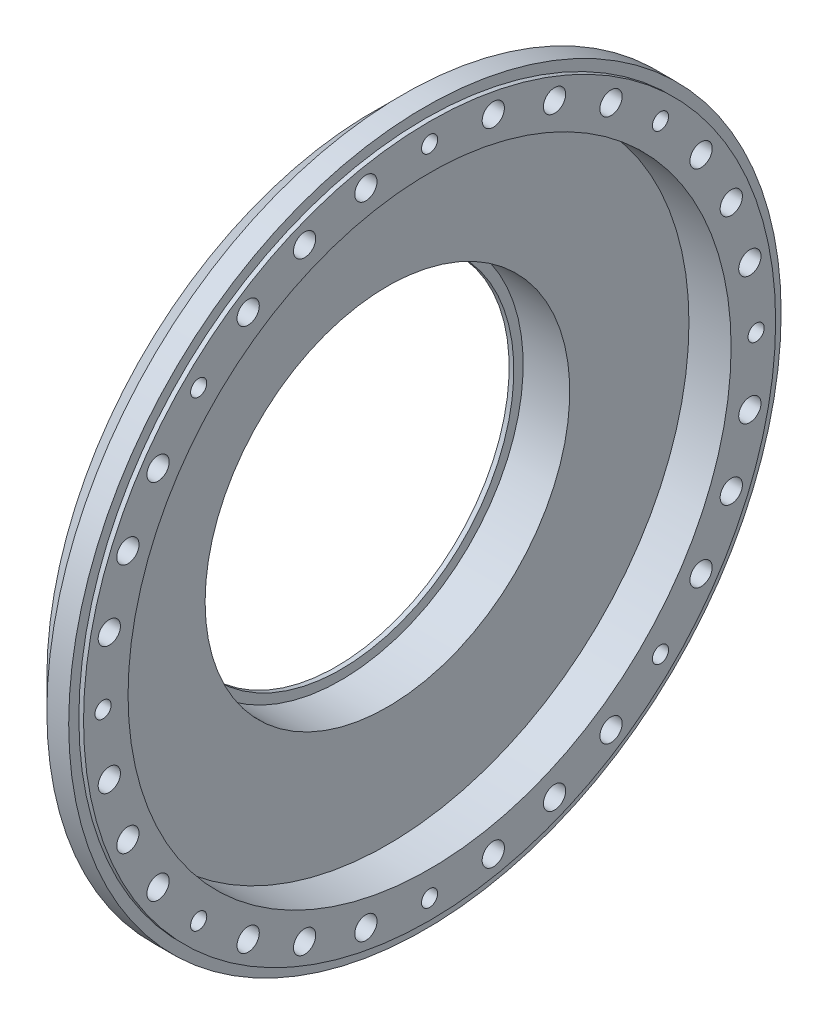
SolidWorks part; units mm, degrees
ref_plane "Front Plane" through (0, 0, 0) normal (0, 0, 1) x (1, 0, 0)
ref_plane "Top Plane" through (0, 0, 0) normal (0, 1, 0) x (1, 0, 0)
ref_plane "Right Plane" through (0, 0, 0) normal (1, 0, 0) x (0, 0, -1)
sketch "Sketch2" plane through (0, 0, 0) normal (0, 0, 1) x (1, 0, 0)
  line L0 (0, 0) -> (58.591, 0) construction
  line L2 (0, 0) -> (18.4, 0)
  line L3 (0, 0) -> (0, 2.5)
  line L4 (0, 2.5) -> (18.4, 2.5)
  line L5 (18.4, 0) -> (18.4, 2.5)
  line L6 (6.0094, 2.5) -> (6.0094, 6)
  line L11 (6.0094, 6) -> (9.9794, 6)
  line L16 (12.9794, 6) -> (12.9794, 3)
  line L17 (12.9794, 3) -> (13.6398, 3)
  line L18 (13.6398, 3) -> (13.6398, 2.5)
  line L19 (13.6398, 2.5) -> (6.0094, 2.5)
  line L22 (13.6398, 2.5) -> (16.1198, 2.5)
  line L23 (13.6398, 2.5) -> (13.6398, 4)
  line L24 (13.6398, 4) -> (16.1198, 4)
  line L25 (16.1198, 2.5) -> (16.1198, 4)
  line L27 (6.0094, 6) -> (9.9794, 6)
  line L28 (6.0094, 6) -> (6.0094, 9)
  line L29 (6.0094, 9) -> (9.9794, 9)
  line L30 (9.9794, 6) -> (9.9794, 9)
  line L31 (6.0094, 9) -> (6.0094, 8.25)
  line L32 (6.0094, 8.25) -> (5.0094, 8.25)
  line L33 (8.6609, 22.001) -> (8.6609, 12.476) construction
  line L34 (5.0094, 12.476) -> (12.3124, 12.476)
  line L35 (9.9794, 9) -> (12.3124, 9)
  line L36 (5.0094, 7.9375) -> (1.8344, 7.9375)
  line L37 (5.0094, 8.25) -> (5.0094, 12.476)
  line L38 (5.0094, 7.9375) -> (5.0094, 13.9365)
  line L39 (5.0094, 13.9365) -> (1.8344, 13.9365)
  line L40 (1.8344, 7.9375) -> (1.8344, 13.9365)
  line L41 (5.0094, 22.001) -> (12.3124, 22.001)
  line L42 (5.0094, 22.001) -> (5.0094, 30.1625)
  line L43 (5.0094, 30.1625) -> (12.3124, 30.1625)
  line L44 (12.3124, 22.001) -> (12.3124, 30.1625)
  line L49 (16.6398, 22.001) -> (16.6398, 7.5)
  line L51 (23.0198, 7.5) -> (23.0198, 6.5)
  line L54 (16.1198, 4) -> (13.6398, 4)
  line L56 (18.0398, 7.5) -> (23.0198, 7.5)
  line L57 (13.3124, 22.001) -> (16.6398, 22.001)
  line L58 (16.1198, 3.5) -> (20.0198, 3.5)
  line L59 (29.9098, 14) -> (26.9098, 11)
  line L60 (4.0094, 31.75) -> (18.0398, 31.75)
  line L61 (18.0398, 7.5) -> (23.0198, 7.5)
  line L62 (18.0398, 7.5) -> (18.0398, 12)
  line L63 (18.0398, 12) -> (23.0198, 12)
  line L64 (23.0198, 7.5) -> (23.0198, 12)
  line L65 (18.0398, 31.75) -> (18.0398, 12)
  line L66 (23.0198, 11) -> (26.9098, 11)
  line L67 (34.8098, 23) -> (31.3098, 19.5)
  line L68 (35.8098, 31) -> (38.7998, 33.99)
  line L69 (29.9098, 14) -> (29.9098, 15)
  line L70 (29.9098, 15) -> (22.9398, 15)
  line L71 (22.9398, 15) -> (21.0398, 15)
  line L72 (18.0398, 7.5) -> (16.6398, 7.5)
  line L73 (21.0398, 15) -> (21.0398, 43)
  line L74 (19.5798, 40) -> (9.6198, 40)
  line L75 (9.6198, 40) -> (4.0094, 40)
  line L76 (21.0398, 43) -> (19.5798, 43)
  line L77 (22.9398, 15) -> (29.9098, 15)
  line L78 (22.9398, 15) -> (22.9398, 21)
  line L79 (22.9398, 21) -> (29.9098, 21)
  line L80 (29.9098, 15) -> (29.9098, 21)
  line L81 (9.6198, 40) -> (19.5798, 40)
  line L82 (9.6198, 40) -> (9.6198, 50)
  line L83 (9.6198, 50) -> (19.5798, 50)
  line L84 (19.5798, 40) -> (19.5798, 50)
  line L85 (4.0094, 40) -> (4.0094, 31.75)
  line L86 (12.9794, 3) -> (12.9794, 2.5)
  line L87 (31.3098, 19.5) -> (29.9098, 19.5)
  line L88 (21.4694, 63.5) -> (21.4694, 51.308)
  line L89 (21.4694, 63.5) -> (25.9398, 63.5)
  line L90 (25.9398, 63.5) -> (25.9398, 25)
  line L91 (27.8398, 25) -> (25.9398, 25)
  line L92 (9.6198, 48) -> (8.1598, 48)
  line L93 (8.1598, 48) -> (8.1598, 53.476)
  line L94 (8.1598, 53.476) -> (19.5798, 53.476)
  line L95 (19.5798, 53.476) -> (19.5798, 50)
  line L96 (13.8698, 63.001) -> (13.8698, 53.476) construction
  line L97 (8.1598, 63.001) -> (19.5798, 63.001)
  line L98 (8.1598, 63.001) -> (8.1598, 68.2625)
  line L99 (8.1598, 68.2625) -> (19.5798, 68.2625)
  line L100 (19.5798, 63.001) -> (19.5798, 68.2625)
  line L101 (12.9794, 6) -> (11.9794, 6)
  line L102 (8.1598, 44.825) -> (4.9848, 44.825)
  line L103 (8.1598, 44.825) -> (8.1598, 54.9365)
  line L104 (8.1598, 54.9365) -> (4.9848, 54.9365)
  line L106 (9.9794, 6) -> (10.8794, 6)
  line L107 (27.8398, 25) -> (34.8098, 25)
  line L108 (34.8098, 25) -> (34.8098, 23)
  line L109 (0, 0) -> (-2, 0)
  line L110 (0, 0) -> (0, 11)
  line L111 (27.8398, 25) -> (34.8098, 25)
  line L112 (27.8398, 25) -> (27.8398, 32.5)
  line L113 (27.8398, 32.5) -> (34.8098, 32.5)
  line L114 (34.8098, 25) -> (34.8098, 32.5)
  line L115 (35.8098, 31) -> (34.8098, 31)
  line L116 (27.8398, 32.5) -> (27.8398, 64.5)
  line L117 (20.5373, 74.025) -> (6.2023, 74.025)
  line L118 (6.2023, 74.025) -> (6.2023, 76.2)
  line L119 (38.7998, 47.29) -> (30.8398, 55.25)
  line L120 (0, 11) -> (-2, 11)
  line L121 (38.7998, 43.815) -> (30.8623, 43.815)
  line L123 (-4.8152, 69.85) -> (1.5348, 76.2)
  line L124 (38.7998, 47.29) -> (38.7998, 33.99)
  line L125 (-2, 0) -> (-2, 11)
  line L126 (38.7998, 37.465) -> (30.8623, 37.465)
  line L127 (30.8623, 43.815) -> (30.8623, 37.465)
  line L128 (6.0094, 2.5) -> (6.0094, 0)
  line L129 (-0.0152, 63.5) -> (-0.0152, 30)
  line L132 (4.9848, 63.5) -> (-0.0152, 63.5)
  line L136 (-1.8152, 30) -> (-11.7752, 30)
  line L138 (-13.7752, 25.4) -> (-2, 25.4)
  line L139 (-2, 25.4) -> (-2, 11.5)
  line L140 (27.8398, 64.5) -> (20.5373, 64.5)
  line L141 (-1.8152, 30) -> (-11.7752, 30)
  line L142 (-1.8152, 30) -> (-1.8152, 39)
  line L143 (-1.8152, 39) -> (-11.7752, 39)
  line L144 (-11.7752, 30) -> (-11.7752, 39)
  line L145 (20.5373, 64.5) -> (20.5373, 74.025)
  line L146 (-12.7752, 37) -> (-12.7752, 47.29)
  line L147 (-12.7752, 37) -> (-11.7752, 37)
  line L148 (30.8398, 55.25) -> (30.8398, 76.2)
  line L149 (11.9794, 6) -> (11.9794, 5.45)
  line L154 (-2, 11.5) -> (0.5, 11.5)
  line L155 (4.9848, 60.6197) -> (24.0348, 60.6197)
  line L160 (4.9848, 60.6197) -> (4.9848, 55.8572)
  line L161 (4.9848, 55.8572) -> (24.0348, 55.8572)
  line L166 (24.0348, 60.6197) -> (24.0348, 55.8572)
  line L167 (4.9848, 60.6197) -> (24.0348, 55.8572) construction
  line L172 (4.9848, 55.8572) -> (24.0348, 60.6197) construction
  line L173 (24.0348, 62.2072) -> (25.9398, 62.2072)
  line L174 (11.9794, 5.45) -> (10.8794, 5.45)
  line L175 (10.8794, 6) -> (10.8794, 5.45)
  line L176 (24.0348, 62.2072) -> (24.0348, 54.2697)
  line L177 (24.0348, 54.2697) -> (25.9398, 54.2697)
  line L178 (25.9398, 62.2072) -> (25.9398, 54.2697)
  line L179 (24.0348, 62.2072) -> (25.9398, 54.2697) construction
  line L180 (24.0348, 54.2697) -> (25.9398, 62.2072) construction
  line L181 (3, 19.6197) -> (15.7, 19.6197)
  line L182 (3, 19.6197) -> (3, 14.8572)
  line L183 (3, 14.8572) -> (15.7, 14.8572)
  line L184 (15.7, 19.6197) -> (15.7, 14.8572)
  line L185 (3, 19.6197) -> (15.7, 14.8572) construction
  line L186 (3, 14.8572) -> (15.7, 19.6197) construction
  line L187 (15.7, 21.2072) -> (16.6398, 21.2072)
  line L188 (15.7, 21.2072) -> (15.7, 13.2697)
  line L189 (15.7, 13.2697) -> (16.6398, 13.2697)
  line L190 (16.6398, 21.2072) -> (16.6398, 13.2697)
  line L191 (15.7, 21.2072) -> (16.6398, 13.2697) construction
  line L192 (15.7, 13.2697) -> (16.6398, 21.2072) construction
  line L193 (0.5, 11.5) -> (0.5, 6.9375)
  line L194 (0.5, 6.9375) -> (1.8344, 6.9375)
  line L195 (23.0198, 6.5) -> (20.0198, 3.5)
  line L196 (4.9848, 63.5) -> (4.9848, 54.9365)
  line L197 (3, 43.825) -> (4.9848, 43.825)
  line L198 (1.8344, 6.9375) -> (1.8344, 7.9375)
  line L199 (6.0094, 0) -> (12.9794, 0)
  line L200 (12.9794, 0) -> (12.9794, 2.5)
  line L201 (18.0398, 31.75) -> (18.0398, 35.875)
  line L202 (18.0398, 35.875) -> (21.0398, 35.875)
  line L203 (30.8398, 76.2) -> (6.2023, 76.2)
  line L204 (2.7573, 69.85) -> (7.2023, 69.85) construction
  line L205 (7.2023, 67.4688) -> (26.2523, 67.4688)
  line L206 (7.2023, 74.025) -> (7.2023, 64.5)
  line L207 (7.2023, 64.5) -> (-1.8152, 64.5)
  line L208 (-1.8152, 64.5) -> (-1.8152, 39)
  line L209 (-12.7752, 47.29) -> (-4.8152, 55.25)
  line L210 (-4.8152, 55.25) -> (-4.8152, 69.85)
  line L211 (7.2023, 67.4688) -> (7.2023, 72.2312)
  line L212 (7.2023, 72.2312) -> (26.2523, 72.2313)
  line L213 (26.2523, 67.4688) -> (26.2523, 72.2313)
  line L214 (26.2523, 73.8187) -> (30.8398, 73.8187)
  line L215 (26.2523, 73.8187) -> (26.2523, 65.8813)
  line L216 (26.2523, 65.8813) -> (30.8398, 65.8813)
  line L217 (30.8398, 73.8187) -> (30.8398, 65.8813)
  line L218 (2.7573, 72.2313) -> (24.9823, 72.2313)
  line L219 (2.7573, 72.2313) -> (2.7573, 67.4687)
  line L220 (2.7573, 67.4687) -> (24.9823, 67.4687)
  line L221 (24.9823, 72.2313) -> (24.9823, 67.4687)
  line L222 (24.9823, 69.85) -> (20.5373, 69.85) construction
  line L223 (21.4694, 51.308) -> (22.9398, 51.308)
  line L224 (22.9398, 51.308) -> (22.9398, 21)
  line L225 (13.6398, 4) -> (13.6398, 12.2697)
  line L226 (13.6398, 12.2697) -> (13.3124, 12.2697)
  line L227 (13.3124, 12.2697) -> (13.3124, 22.001)
  line L228 (12.3124, 9) -> (12.3124, 12.476)
  line L229 (-1.8152, 30) -> (-0.0152, 30)
  line L230 (8.1598, 65.6317) -> (2.7573, 65.6317) construction
  line L231 (19.5798, 65.6317) -> (24.9823, 65.6317) construction
  line L232 (1.5348, 76.2) -> (6.2023, 76.2)
  line L233 (-11.7752, 30) -> (-13.7752, 30)
  line L234 (-13.7752, 30) -> (-13.7752, 25.4)
  line L235 (3, 13.9365) -> (3, 43.825)
  line L236 (4.9848, 54.9365) -> (4.9848, 44.825)
  line L237 (4.9848, 43.825) -> (4.9848, 44.825)
  circle A0 centre (26.8898, 25.95) radius 0.95
  circle A1 centre (21.9898, 15.95) radius 0.95
  circle A2 centre (17.3398, 8.2) radius 0.7
  circle A3 centre (10.4294, 6.45) radius 0.45
  circle A4 centre (-0.9152, 30.9) radius 0.9
  point P7 (24.9873, 58.2385)
  point P131 (16.1699, 17.2385)
  point P135 (14.5098, 58.2385)
  point P146 (9.35, 17.2385)
sketch "Sketch3" plane through (0, 0, 0) normal (1, 0, 0) x (0, 0, -1)
  line L0 (0, 0) -> (0, 69.85) construction
  line L1 (0, 0) -> (13.6271, 68.5079) construction
  line L2 (0, 0) -> (0, 58.2385) construction
  line L3 (0, 0) -> (50.436, 29.1192) construction
  line L4 (0, 0) -> (0, 31.75) construction
  line L5 (0, 0) -> (12.1502, 29.3332) construction
  line L6 (0, 0) -> (0, 17.2385) construction
  line L7 (0, 0) -> (14.929, 8.6192) construction
  line L8 (0, 0) -> (0, 58.2385) construction
  line L9 (0, 0) -> (50.436, 29.1192) construction
  line L10 (0, 0) -> (5.9583, 29.9542) construction
  line L11 (0, 0) -> (16.9677, 25.394) construction
  circle A0 centre (0, 0) radius 69.85 construction
  circle A1 centre (0, 0) radius 58.2385 construction
  circle A2 centre (0, 0) radius 31.75 construction
  circle A3 centre (0, 0) radius 17.2385 construction
  circle A4 centre (0, 69.85) radius 3.175
  circle A5 centre (0, 58.2385) radius 4.7625
  circle A6 centre (0, 31.75) radius 3.175
  circle A7 centre (0, 17.2385) radius 4.7625
  circle A8 centre (13.6271, 68.5079) radius 3.175
  circle A9 centre (26.7304, 64.533) radius 3.175
  circle A10 centre (38.8066, 58.0782) radius 3.175
  circle A11 centre (49.3914, 49.3914) radius 3.175
  circle A12 centre (58.0782, 38.8066) radius 3.175
  circle A13 centre (64.533, 26.7304) radius 3.175
  circle A14 centre (68.5079, 13.6271) radius 3.175
  circle A15 centre (69.85, 0) radius 3.175
  circle A16 centre (68.5079, -13.6271) radius 3.175
  circle A17 centre (64.533, -26.7304) radius 3.175
  circle A18 centre (58.0782, -38.8066) radius 3.175
  circle A19 centre (49.3914, -49.3914) radius 3.175
  circle A20 centre (38.8066, -58.0782) radius 3.175
  circle A21 centre (26.7304, -64.533) radius 3.175
  circle A22 centre (13.6271, -68.5079) radius 3.175
  circle A23 centre (0, -69.85) radius 3.175
  circle A24 centre (-13.6271, -68.5079) radius 3.175
  circle A25 centre (-26.7304, -64.533) radius 3.175
  circle A26 centre (-38.8066, -58.0782) radius 3.175
  circle A27 centre (-49.3914, -49.3914) radius 3.175
  circle A28 centre (-58.0782, -38.8066) radius 3.175
  circle A29 centre (-64.533, -26.7304) radius 3.175
  circle A30 centre (-68.5079, -13.6271) radius 3.175
  circle A31 centre (-69.85, 0) radius 3.175
  circle A32 centre (-68.5079, 13.6271) radius 3.175
  circle A33 centre (-64.533, 26.7304) radius 3.175
  circle A34 centre (-58.0782, 38.8066) radius 3.175
  circle A35 centre (-49.3914, 49.3914) radius 3.175
  circle A36 centre (-38.8066, 58.0782) radius 3.175
  circle A37 centre (-26.7304, 64.533) radius 3.175
  circle A38 centre (-13.6271, 68.5079) radius 3.175
  circle A47 centre (50.436, 29.1192) radius 4.7625
  circle A48 centre (50.436, -29.1192) radius 4.7625
  circle A49 centre (0, -58.2385) radius 4.7625
  circle A50 centre (-50.436, -29.1192) radius 4.7625
  circle A51 centre (-50.436, 29.1192) radius 4.7625
  circle A58 centre (12.1502, 29.3332) radius 3.175
  circle A59 centre (22.4506, 22.4506) radius 3.175
  circle A60 centre (29.3332, 12.1502) radius 3.175
  circle A61 centre (31.75, 0) radius 3.175
  circle A62 centre (29.3332, -12.1502) radius 3.175
  circle A63 centre (22.4506, -22.4506) radius 3.175
  circle A64 centre (12.1502, -29.3332) radius 3.175
  circle A65 centre (0, -31.75) radius 3.175
  circle A66 centre (-12.1502, -29.3332) radius 3.175
  circle A67 centre (-22.4506, -22.4506) radius 3.175
  circle A68 centre (-29.3332, -12.1502) radius 3.175
  circle A69 centre (-31.75, 0) radius 3.175
  circle A70 centre (-29.3332, 12.1502) radius 3.175
  circle A71 centre (-22.4506, 22.4506) radius 3.175
  circle A72 centre (14.929, 8.6192) radius 4.7625
  circle A73 centre (14.929, -8.6192) radius 4.7625
  circle A74 centre (0, -17.2385) radius 4.7625
  circle A75 centre (-14.929, -8.6192) radius 4.7625
  circle A76 centre (-14.929, 8.6192) radius 4.7625
  circle A77 centre (0, 0) radius 50
  circle A78 centre (0, 0) radius 9
  circle A79 centre (-12.1502, 29.3332) radius 3.175
  circle A80 centre (0, 0) radius 76.2
  circle A81 centre (0, 0) radius 74.025
  circle A82 centre (0, 69.85) radius 3.9687
  circle A83 centre (49.3914, 49.3914) radius 3.9687
  circle A84 centre (69.85, 0) radius 3.9688
  circle A85 centre (49.3914, -49.3914) radius 3.9687
  circle A86 centre (0, -69.85) radius 3.9687
  circle A87 centre (-49.3914, -49.3914) radius 3.9687
  circle A88 centre (-69.85, 0) radius 3.9688
  circle A89 centre (-49.3914, 49.3914) radius 3.9687
  circle A90 centre (0, 69.85) radius 2.3812
  circle A91 centre (13.6271, 68.5079) radius 2.3812
  circle A92 centre (26.7304, 64.533) radius 2.3813
  circle A93 centre (38.8066, 58.0782) radius 2.3812
  circle A94 centre (49.3914, 49.3914) radius 2.3812
  circle A95 centre (58.0782, 38.8066) radius 2.3812
  circle A96 centre (64.533, 26.7304) radius 2.3813
  circle A97 centre (68.5079, 13.6271) radius 2.3813
  circle A98 centre (69.85, 0) radius 2.3813
  circle A99 centre (68.5079, -13.6271) radius 2.3813
  circle A100 centre (64.533, -26.7304) radius 2.3813
  circle A101 centre (58.0782, -38.8066) radius 2.3812
  circle A102 centre (49.3914, -49.3914) radius 2.3812
  circle A103 centre (38.8066, -58.0782) radius 2.3812
  circle A104 centre (26.7304, -64.533) radius 2.3813
  circle A105 centre (13.6271, -68.5079) radius 2.3812
  circle A106 centre (0, -69.85) radius 2.3812
  circle A107 centre (-13.6271, -68.5079) radius 2.3812
  circle A108 centre (-26.7304, -64.533) radius 2.3813
  circle A109 centre (-38.8066, -58.0782) radius 2.3812
  circle A110 centre (-49.3914, -49.3914) radius 2.3812
  circle A111 centre (-58.0782, -38.8066) radius 2.3812
  circle A112 centre (-64.533, -26.7304) radius 2.3812
  arc A113 (3.0399, 30.8338) -> (8.9911, 29.65) centre (5.9583, 29.9542) cw
  arc A114 (14.6081, 27.3234) -> (19.6532, 23.9523) centre (16.9677, 25.394) cw
  arc A115 (23.9523, 19.6532) -> (27.3234, 14.6081) centre (25.394, 16.9677) cw
  arc A116 (29.65, 8.9911) -> (30.8338, 3.0399) centre (29.9542, 5.9583) cw
  arc A117 (30.8338, -3.0399) -> (29.65, -8.9911) centre (29.9542, -5.9583) cw
  arc A118 (27.3234, -14.6081) -> (23.9523, -19.6532) centre (25.394, -16.9677) cw
  arc A119 (19.6532, -23.9523) -> (14.6081, -27.3234) centre (16.9677, -25.394) cw
  arc A120 (8.9911, -29.65) -> (3.0399, -30.8338) centre (5.9583, -29.9542) cw
  arc A121 (-3.0399, -30.8338) -> (-8.9911, -29.65) centre (-5.9583, -29.9542) cw
  arc A122 (-14.6081, -27.3234) -> (-19.6532, -23.9523) centre (-16.9677, -25.394) cw
  arc A123 (-23.9523, -19.6532) -> (-27.3234, -14.6081) centre (-25.394, -16.9677) cw
  arc A124 (-29.65, -8.9911) -> (-30.8338, -3.0399) centre (-29.9542, -5.9583) cw
  arc A125 (-30.8338, 3.0399) -> (-29.65, 8.9911) centre (-29.9542, 5.9583) cw
  arc A126 (-27.3234, 14.6081) -> (-23.9523, 19.6532) centre (-25.394, 16.9677) cw
  arc A127 (-19.6532, 23.9523) -> (-14.6081, 27.3234) centre (-16.9677, 25.394) cw
  arc A128 (-8.9911, 29.65) -> (-3.0399, 30.8338) centre (-5.9583, 29.9542) cw
  arc A129 (26.9875, 0) -> (26.9932, 0.1932) centre (30.2705, 0) cw
  arc A130 (65.0988, 0.2771) -> (65.0875, 0) centre (68.4964, 0) ccw
  circle A131 centre (1.5875, 0) radius 40
  circle A132 centre (1.5875, 0) radius 2.5
  circle A133 centre (1.5875, 0) radius 3
  circle A134 centre (1.5875, 0) radius 43
  circle A135 centre (-68.5079, -13.6271) radius 2.3813
  circle A136 centre (-69.85, 0) radius 2.3813
  circle A137 centre (-68.5079, 13.6271) radius 2.3813
  circle A138 centre (-64.533, 26.7304) radius 2.3812
  circle A139 centre (-58.0782, 38.8066) radius 2.3812
  circle A140 centre (-49.3914, 49.3914) radius 2.3812
  circle A141 centre (-38.8066, 58.0782) radius 2.3812
  circle A142 centre (-26.7304, 64.533) radius 2.3813
  circle A143 centre (-13.6271, 68.5079) radius 2.3812
  circle A144 centre (0, 58.2385) radius 2.3812
  circle A145 centre (0, 58.2385) radius 3.9688
  circle A146 centre (50.436, 29.1192) radius 3.9688
  circle A147 centre (50.436, 29.1192) radius 2.3813
  circle A148 centre (50.436, -29.1192) radius 3.9687
  circle A149 centre (50.436, -29.1192) radius 2.3812
  circle A150 centre (0, -58.2385) radius 3.9687
  circle A151 centre (0, -58.2385) radius 2.3812
  circle A152 centre (-50.436, -29.1192) radius 3.9687
  circle A153 centre (-50.436, -29.1192) radius 2.3812
  circle A154 centre (-50.436, 29.1192) radius 3.9687
  circle A155 centre (-50.436, 29.1192) radius 2.3812
  spline S1 degree 4 number of poles 499 (26.9875, 0) -> (26.9932, 0.1932)
  spline S3 degree 4 number of poles 617 (65.0875, 0) -> (65.0988, 0.2771)
  point P116 (0, 0)
  point P225 (0, 0)
sketch "Sketch4" plane through (0, 0, 0) normal (0, 0, 1) x (1, 0, 0)
  line L0 (20.5373, 74.025) -> (6.2023, 74.025) construction
  line L1 (6.2023, 74.025) -> (6.2023, 76.2) construction
  line L2 (7.2023, 74.025) -> (7.2023, 64.5) construction
  line L3 (7.2023, 64.5) -> (-1.8152, 64.5) construction
  line L4 (-1.8152, 64.5) -> (-1.8152, 39) construction
  line L5 (-11.7752, 30) -> (-11.7752, 39) construction
  line L6 (-1.8152, 39) -> (-11.7752, 39) construction
  line L7 (-12.7752, 37) -> (-11.7752, 37) construction
  line L8 (-12.7752, 37) -> (-12.7752, 47.29) construction
  line L9 (-12.7752, 47.29) -> (-4.8152, 55.25) construction
  line L10 (-4.8152, 55.25) -> (-4.8152, 69.85) construction
  line L12 (7.2023, 74.025) -> (6.2023, 74.025)
  line L13 (6.2023, 74.025) -> (6.2023, 76.2)
  line L14 (7.2023, 74.025) -> (7.2023, 64.5)
  line L15 (7.2023, 64.5) -> (-1.8152, 64.5)
  line L16 (-1.8152, 64.5) -> (-1.8152, 39)
  line L17 (-11.7752, 37) -> (-11.7752, 39)
  line L18 (-1.8152, 39) -> (-11.7752, 39)
  line L19 (-12.7752, 37) -> (-11.7752, 37)
  line L20 (-12.7752, 37) -> (-12.7752, 47.29)
  line L21 (-12.7752, 47.29) -> (-4.8152, 55.25)
  line L22 (-4.8152, 55.25) -> (-4.8152, 69.85)
  line L24 (-4.8152, 69.85) -> (1.5348, 76.2) construction
  line L25 (1.5348, 76.2) -> (6.2023, 76.2) construction
  line L26 (-4.8152, 69.85) -> (1.5348, 76.2)
  line L27 (1.5348, 76.2) -> (6.2023, 76.2)
revolve "Revolve1" add sketch "Sketch4" angle 360 about L0
sketch "Sketch5" plane through (7.2023, 0, 0) normal (1, 0, 0) x (0, 0, -1)
  circle A0 centre (13.6271, 68.5079) radius 2.3812 construction
  circle A1 centre (26.7304, 64.533) radius 2.3813 construction
  circle A2 centre (38.8066, 58.0782) radius 2.3813 construction
  circle A3 centre (58.0782, 38.8066) radius 2.3812 construction
  circle A4 centre (64.533, 26.7304) radius 2.3813 construction
  circle A5 centre (68.5079, 13.6271) radius 2.3813 construction
  circle A6 centre (68.5079, -13.6271) radius 2.3813 construction
  circle A7 centre (64.533, -26.7304) radius 2.3813 construction
  circle A8 centre (58.0782, -38.8066) radius 2.3813 construction
  circle A9 centre (38.8066, -58.0782) radius 2.3812 construction
  circle A10 centre (26.7304, -64.533) radius 2.3813 construction
  circle A11 centre (13.6271, -68.5079) radius 2.3812 construction
  circle A12 centre (-13.6271, -68.5079) radius 2.3812 construction
  circle A13 centre (-26.7304, -64.533) radius 2.3813 construction
  circle A14 centre (-38.8066, -58.0782) radius 2.3812 construction
  circle A15 centre (-58.0782, -38.8066) radius 2.3812 construction
  circle A16 centre (-64.533, -26.7304) radius 2.3813 construction
  circle A17 centre (-68.5079, -13.6271) radius 2.3813 construction
  circle A18 centre (-68.5079, 13.6271) radius 2.3813 construction
  circle A19 centre (-64.533, 26.7304) radius 2.3813 construction
  circle A20 centre (-58.0782, 38.8066) radius 2.3813 construction
  circle A21 centre (-38.8066, 58.0782) radius 2.3812 construction
  circle A22 centre (-26.7304, 64.533) radius 2.3813 construction
  circle A23 centre (-13.6271, 68.5079) radius 2.3812 construction
  circle A24 centre (13.6271, 68.5079) radius 2.3812
  circle A25 centre (26.7304, 64.533) radius 2.3813
  circle A26 centre (38.8066, 58.0782) radius 2.3812
  circle A27 centre (58.0782, 38.8066) radius 2.3812
  circle A28 centre (64.533, 26.7304) radius 2.3813
  circle A29 centre (68.5079, 13.6271) radius 2.3813
  circle A30 centre (68.5079, -13.6271) radius 2.3813
  circle A31 centre (64.533, -26.7304) radius 2.3813
  circle A32 centre (58.0782, -38.8066) radius 2.3812
  circle A33 centre (38.8066, -58.0782) radius 2.3812
  circle A34 centre (26.7304, -64.533) radius 2.3813
  circle A35 centre (13.6271, -68.5079) radius 2.3812
  circle A36 centre (-13.6271, -68.5079) radius 2.3812
  circle A37 centre (-26.7304, -64.533) radius 2.3813
  circle A38 centre (-38.8066, -58.0782) radius 2.3812
  circle A39 centre (-58.0782, -38.8066) radius 2.3812
  circle A40 centre (-64.533, -26.7304) radius 2.3812
  circle A41 centre (-68.5079, -13.6271) radius 2.3813
  circle A42 centre (-68.5079, 13.6271) radius 2.3813
  circle A43 centre (-64.533, 26.7304) radius 2.3812
  circle A44 centre (-58.0782, 38.8066) radius 2.3812
  circle A45 centre (-38.8066, 58.0782) radius 2.3812
  circle A46 centre (-26.7304, 64.533) radius 2.3813
  circle A47 centre (-13.6271, 68.5079) radius 2.3812
extrude "Cut-Extrude1" cut sketch "Sketch5" against normal up to vertex (4.445 mm away) up to point (2.7573, 72.2313, 0)
sketch "Sketch6" plane through (7.2023, 0, 0) normal (1, 0, 0) x (0, 0, -1)
  circle A0 centre (49.3914, -49.3914) radius 3.9688 construction
  circle A1 centre (0, 0) radius 74.025
  circle A2 centre (0, 0) radius 74.025
  circle A3 centre (69.85, 0) radius 3.9688 construction
  circle A4 centre (49.3914, 49.3914) radius 3.9687 construction
  circle A5 centre (0, 69.85) radius 3.9687 construction
  circle A6 centre (-49.3914, 49.3914) radius 3.9687 construction
  circle A7 centre (-69.85, 0) radius 3.9688 construction
  circle A8 centre (-49.3914, -49.3914) radius 3.9688 construction
  circle A9 centre (0, -69.85) radius 3.9687 construction
  circle A10 centre (49.3914, -49.3914) radius 3.9687
  circle A11 centre (69.85, 0) radius 3.9688
  circle A12 centre (49.3914, 49.3914) radius 3.9687
  circle A13 centre (0, 69.85) radius 3.9687
  circle A14 centre (-49.3914, 49.3914) radius 3.9687
  circle A15 centre (-69.85, 0) radius 3.9688
  circle A16 centre (-49.3914, -49.3914) radius 3.9687
  circle A17 centre (0, -69.85) radius 3.9687
  circle A18 centre (0, 69.85) radius 1.7272
  circle A19 centre (49.3914, 49.3914) radius 1.7272
  circle A20 centre (69.85, 0) radius 1.7272
  circle A21 centre (49.3914, -49.3914) radius 1.7272
  circle A22 centre (0, -69.85) radius 1.7272
  circle A23 centre (-49.3914, -49.3914) radius 1.7272
  circle A24 centre (-69.85, 0) radius 1.7272
  circle A25 centre (-49.3914, 49.3914) radius 1.7272
  dimension "D2" = 3.4544
  dimension "D1" = 0
extrude "Cut-Extrude2" cut sketch "Sketch6" against normal blind 9.525 contours A18 | A25 | A24 | A23 | A22 | A21 | A20 | A19 region at (7.2023, 69.85, 0) region at (7.2023, 49.3914, -49.3914) region at (7.2023, 0, -69.85) region at (7.2023, -49.3914, -49.3914) region at (7.2023, -69.85, 0) region at (7.2023, -49.3914, 49.3914) region at (7.2023, 0, 69.85) region at (7.2023, 49.3914, 49.3914)
